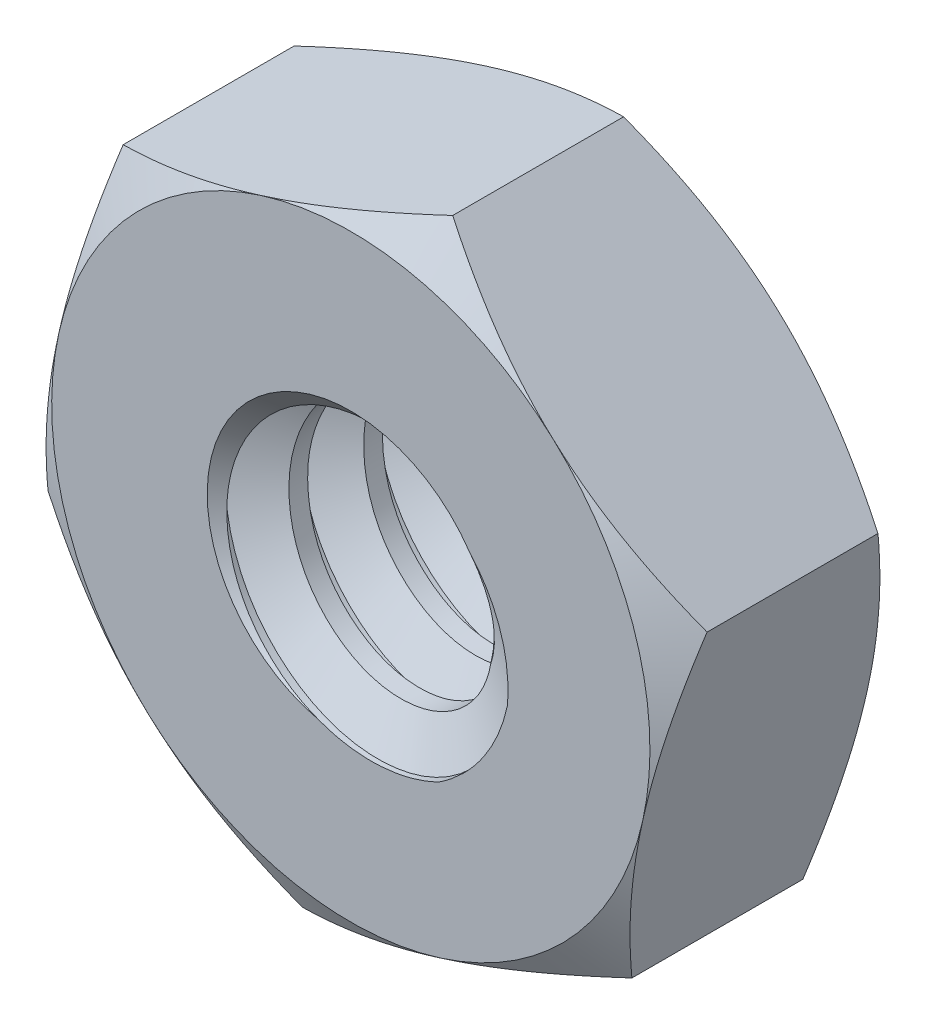
SolidWorks part; units mm, degrees
ref_plane "Front Plane" through (0, 0, 0) normal (0, 0, 1) x (1, 0, 0)
ref_plane "Top Plane" through (0, 0, 0) normal (0, 1, 0) x (1, 0, 0)
ref_plane "Right Plane" through (0, 0, 0) normal (1, 0, 0) x (0, 0, -1)
sketch "Sketch1" plane through (0, 0, 0) normal (0, 0, 1) x (1, 0, 0)
  line L1 (2.7, -2.4801) -> (3.4978, 1.0982)
  line L2 (3.4978, 1.0982) -> (0.7978, 3.5783)
  line L3 (0.7978, 3.5783) -> (-2.7, 2.4801)
  line L4 (-2.7, 2.4801) -> (-3.4978, -1.0982)
  line L5 (-3.4978, -1.0982) -> (-0.7978, -3.5783)
  line L6 (-0.7978, -3.5783) -> (2.7, -2.4801)
  circle A0 centre (0, 0) radius 3.175 construction
  dimension "D1" = 6.35
  dimension "D2" = 0.7978
extrude "Boss-Extrude1" add sketch "Sketch1" along normal blind 2.3813
sketch "Sketch7" plane through (0, 0, 0) normal (0, 0, -1) x (-1, 0, 0)
  circle A0 centre (0, 0) radius 1.27
  dimension "D1" = 2.54
extrude "Cut-Extrude1" cut sketch "Sketch7" against normal through all
sketch "Sketch13" plane through (0, 0, 0) normal (0, 0, -1) x (-1, 0, 0)
  circle A0 centre (0, 0) radius 3.175
  dimension "D1" = 6.35
extrude "Cut-Extrude2" cut sketch "Sketch13" against normal blind 2.3813 draft 60 flip side to cut
sketch "Sketch14" plane through (0, 0, 2.3813) normal (0, 0, 1) x (1, 0, 0)
  line L0 (0, 0) -> (0.7978, 3.5783) construction
  circle A0 centre (0, 0) radius 3.175
  dimension "D1" = 6.35
extrude "Cut-Extrude3" cut sketch "Sketch14" against normal blind 2.3813 draft 60 flip side to cut
chamfer "Chamfer1" distance 0.254 angle 45 2 edges at (-1.27, 0, 2.3813) (-1.27, 0, 0)
thread "Thread2" pitch 0.7937 method cut profile "Thread Profile3" start angle 0, offset 1.27, length 0, pitch 0.7937, diameter 2.54
ref_plane "Plane3" through (1.27, 0, -1.016) normal (0, -1, 0) x (1, 0, 0)
sketch "Thread Profile3" plane through (1.27, 0, -1.016) normal (0, -1, 0) x (1, 0, 0)
  line L0 (0, 0) -> (0, 0.7937) construction
  line L1 (0, 0) -> (0.4296, 0.248)
  line L2 (0.4296, 0.248) -> (0.4296, 0.3473)
  line L3 (0.4296, 0.3473) -> (0, 0.5953)
  line L4 (0.4296, 0.2977) -> (0, 0.2977) construction
  line L11 (0, 0) -> (0, 0.5953)
  point P2 (0, 0)
  dimension "Pitch" = 0.7937
  dimension "Profile_Angle" = 60
  dimension "Profile_Land" = 0.0992
  dimension "Profile_Height" = 0.4296
